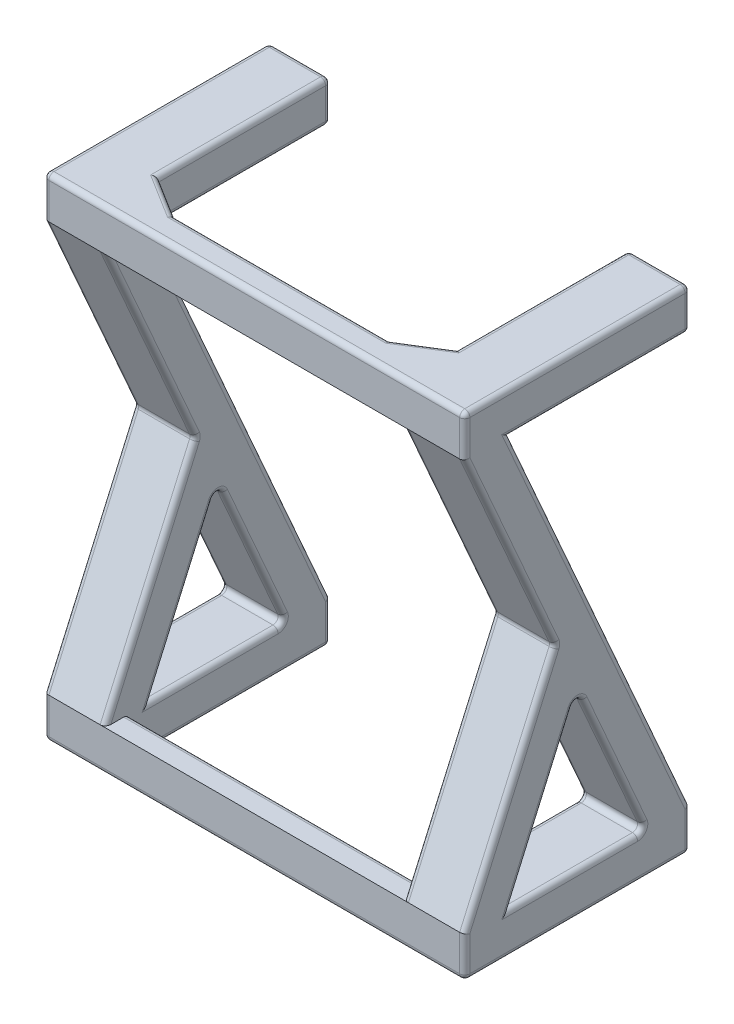
SolidWorks part; units mm, degrees
ref_plane "Front Plane" through (0, 0, 0) normal (0, 0, 1) x (1, 0, 0)
ref_plane "Top Plane" through (0, 0, 0) normal (0, 1, 0) x (1, 0, 0)
ref_plane "Right Plane" through (0, 0, 0) normal (1, 0, 0) x (0, 0, -1)
sketch "Sketch2" plane through (0, 0, 0) normal (0, 1, 0) x (1, 0, 0)
  line L0 (-32.6073, 0) -> (32.6073, 0)
  line L1 (-32.6073, 0) -> (-32.6073, 34.925)
  line L2 (-32.6073, 34.925) -> (-23.0823, 34.925)
  line L3 (-23.0823, 34.925) -> (-23.0823, 9.525)
  line L4 (-23.0823, 9.525) -> (23.0822, 9.525)
  line L5 (23.0822, 9.525) -> (23.0822, 34.925)
  line L6 (23.0822, 34.925) -> (32.6072, 34.925)
  line L7 (32.6072, 34.925) -> (32.6073, 0)
  point P3 (0, 0)
  dimension "D1" = 9.525
  dimension "D2" = 9.525
  dimension "D3" = 46.1645
  dimension "D4" = 25.4
extrude "Boss-Extrude1" add sketch "Sketch2" along normal blind 76.2
sketch "Sketch5" plane through (-32.6073, 0, 0) normal (-1, 0, 0) x (0, 0, 1)
  line L9 (0, 38.1) -> (-34.925, 38.1) construction
  line L10 (-34.925, 76.2) -> (0, 76.2) construction
  line L11 (-34.925, 76.2) -> (-34.925, 0) construction
  line L14 (-34.925, 38.1) -> (-34.925, 69.85)
  line L18 (0, 76.2) -> (0, 0) construction
  line L22 (-27.9857, 6.35) -> (-17.4625, 30.2272)
  line L23 (-17.4625, 30.2272) -> (-6.9393, 6.35)
  line L24 (-27.9857, 6.35) -> (-6.9393, 6.35)
  line L26 (-6.9393, 69.85) -> (-34.925, 6.35)
  line L27 (-34.925, 38.1) -> (-34.925, 6.35)
  line L28 (0, 69.85) -> (0, 6.35)
  line L29 (0, 69.85) -> (-13.9928, 38.1)
  line L30 (-13.9928, 38.1) -> (0, 6.35)
  line L31 (-6.9393, 69.85) -> (-34.925, 69.85)
  point P7 (-17.4625, 38.1)
  point P8 (0, 0)
  point P12 (-12.1492, 38.1)
  point P13 (-6.9385, 69.85)
  dimension "D1" = 6.35
  dimension "D2" = 6.35
  dimension "D3" = 6.35
  dimension "D4" = 6.35
extrude "Cut-Extrude2" cut sketch "Sketch5" against normal through all
sketch "Sketch6" plane through (0, 0, 0) normal (0, 0, 1) x (1, 0, 0)
  line L1 (-23.0823, 69.85) -> (23.0822, 69.85)
  line L2 (-23.0823, 69.85) -> (-23.0822, 6.35)
  line L3 (-23.0822, 6.35) -> (23.0822, 6.35)
  line L4 (23.0822, 69.85) -> (23.0822, 6.35)
  line L13 (32.6073, 6.35) -> (-32.6073, 6.35) construction
  line L14 (-23.0823, 38.1) -> (-23.0823, 27.9624) construction
  line L15 (23.0822, 27.9624) -> (23.0822, 38.1) construction
  line L16 (32.6073, 69.85) -> (-32.6073, 69.85) construction
  point P9 (-23.0187, 6.35)
  point P12 (-23.0187, 69.85)
extrude "Cut-Extrude3" cut sketch "Sketch6" against normal through all
chamfer "Chamfer1" distance 6.35 angle 45 1 edges at (0, 6.35, -9.525)
sketch "Sketch3" plane through (0, 0, -34.925) normal (0, 0, -1) x (-1, 0, 0)
  line L0 (-32.6073, 76.2) -> (-32.6073, 69.85) construction
  line L1 (-23.0823, 6.35) -> (-32.6073, 0) construction
  line L2 (-32.6073, 76.2) -> (-23.0823, 76.2) construction
  circle A0 centre (-27.8448, 73.025) radius 1.905
  circle A1 centre (-27.8448, 3.175) radius 1.905
  point P8 (-27.8448, 76.2)
  point P11 (0, 0)
  point P12 (-32.6073, 73.025)
  point P15 (-27.8448, 3.175)
  dimension "D1" = 3.81
extrude "Cut-Extrude1" cut sketch "Sketch3" against normal blind 12.7
mirror "Mirror1" about plane through (0, 0, 0) normal (1, 0, 0) of "Cut-Extrude1"
sketch "Sketch7" plane through (0, 76.2, 0) normal (0, 1, 0) x (1, 0, 0)
  line L0 (23.0822, 9.525) -> (23.0822, 8.255)
  line L1 (16.6688, 4.2545) -> (-16.6687, 4.2545)
  line L2 (-16.6687, 4.2545) -> (-23.0823, 8.255)
  line L3 (-23.0823, 8.255) -> (-23.0823, 9.525)
  line L4 (23.0822, 8.255) -> (16.6688, 4.2545)
  line L5 (-32.6073, 0) -> (32.6073, 0) construction
  line L6 (23.0822, 9.525) -> (-23.0823, 9.525)
  dimension "D1" = 4.2545
  dimension "D2" = 1.27
  dimension "D3" = 33.3375
extrude "Cut-Extrude4" cut sketch "Sketch7" against normal up to surface (6.35 mm away) up to face at (0, 69.85, -15.5423)
fillet "Fillet1" radius 0.7937 68 edges at (27.8447, 0, -34.925) (32.6073, 0, -17.4625) (0, 0, 0) (-32.6073, 0, -17.4625) (32.6073, 76.2, -17.4625) (0, 6.35, -3.175) (-32.6073, 73.025, -34.925) (-23.0823, 73.025, -34.925) (23.0822, 73.025, -34.925) (32.6073, 73.025, -34.925) (32.6073, 73.025, 0) (-32.6073, 73.025, 0) (27.8447, 76.2, -34.925) (-19.8755, 76.2, -6.2547) (0, 76.2, -4.2545) (19.8755, 76.2, -6.2548) (19.8755, 69.85, -6.2548) (0, 69.85, -4.2545) (-19.8755, 69.85, -6.2547) (23.0822, 76.2, -21.59) (-32.6073, 3.175, -34.925) (-23.0823, 3.175, -34.925) (-27.8448, 6.35, -34.925) (-27.8448, 69.85, -34.925) (-23.0823, 76.2, -21.59) (-23.0823, 53.975, -6.9964) (-23.0822, 22.225, -6.9964) (-23.0822, 18.2886, -12.2009) (-23.0823, 18.2886, -22.7241) (-27.8448, 76.2, -34.925) (23.0822, 3.175, -34.925) (32.6073, 3.175, -34.925) (32.6073, 3.175, 0) (-32.6073, 3.175, 0) (-32.6073, 76.2, -17.4625) (27.8448, 6.35, -34.925) (27.8448, 69.85, -34.925) (32.6073, 69.85, -20.9322) (23.0822, 38.1, -20.9322) (32.6073, 38.1, -20.9322) (-23.0823, 38.1, -20.9322) (-32.6073, 38.1, -20.9322) (-32.6073, 69.85, -20.9322) (32.6073, 6.35, -17.4625) (27.8448, 6.35, -27.9857) (23.0822, 18.2886, -22.7241) (32.6073, 18.2886, -22.7241) (-27.8448, 6.35, -27.9857) (27.8447, 30.2272, -17.4625) (23.0822, 18.2886, -12.2009) (-27.8448, 30.2272, -17.4625) (32.6073, 18.2886, -12.2009) (-32.6073, 6.35, -17.4625) (-32.6073, 18.2886, -12.2009) (-32.6073, 18.2886, -22.7241) (23.0822, 22.225, -6.9964) (32.6073, 22.225, -6.9964) (27.8447, 38.1, -13.9928) (23.0822, 53.975, -6.9964) (-27.8448, 38.1, -13.9928) (32.6073, 53.975, -6.9964) (-32.6073, 22.225, -6.9964) (-32.6073, 53.975, -6.9964) (-27.8448, 0, -34.925) (0, 76.2, 0) (-23.0823, 0, -22.225) (0, 0, -9.525) (23.0822, 0, -22.225)
